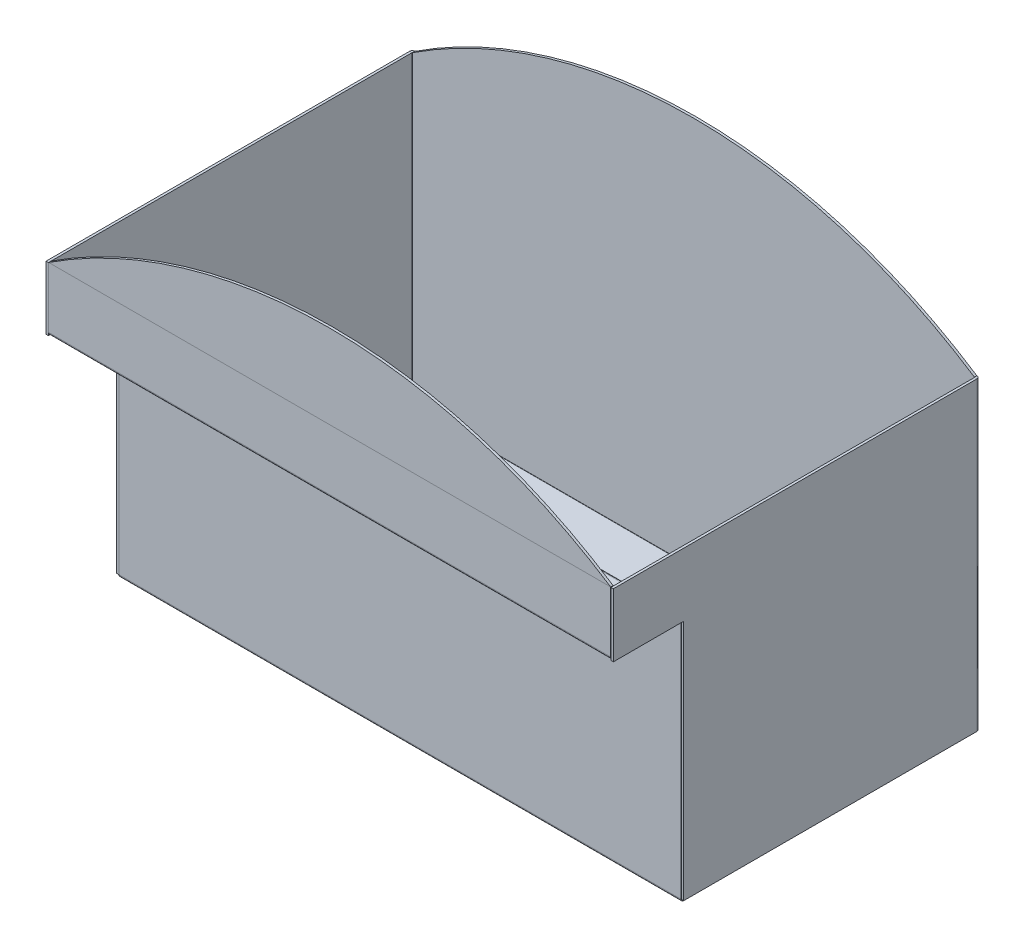
SolidWorks part; units mm, degrees
note: The reader was unsure of these and kept them because the rebuilt part matched: flange length of "Ребро-кромка1", "Ребро-кромка2", "Ребро-кромка3", "Ребро-кромка4", "Ребро-кромка5", "Ребро-кромка6".
ref_plane "Спереди" through (0, 0, 0) normal (0, 0, 1) x (1, 0, 0)
ref_plane "Сверху" through (0, 0, 0) normal (0, 1, 0) x (1, 0, 0)
ref_plane "Справа" through (0, 0, 0) normal (1, 0, 0) x (0, 0, -1)
sketch "Эскиз1" plane through (0, 0, 0) normal (0, 0, 1) x (1, 0, 0)
  line L3 (-97.6801, -33.9236) -> (134.0604, -33.9236)
  arc A0 (-97.6801, -33.9236) -> (134.0604, -33.9236) centre (18.1902, -211.1344) cw
extrude "Вытянуть1" add sketch "Эскиз1" along normal blind 1
sketch "Эскиз5" plane through (0, 0, 0) normal (0, 0, -1) x (-1, 0, 0)
  line L1 (-134.0604, -33.9236) -> (97.6801, -33.9236)
  line L2 (-134.0604, -33.9236) -> (-134.0604, -58.9236)
  line L3 (-134.0604, -58.9236) -> (97.6801, -58.9236)
  line L4 (97.6801, -33.9236) -> (97.6801, -58.9236)
sheet metal parameters "Листовой металл1" thickness 1 parameters "D1"=0.1
base flange "Базовая кромка1" sketch "Эскиз5" thickness 1 reverse thickness direction no parameters "D1"=0.1
edge flange "Ребро-кромка1" sketch "Эскиз9" flange angle 90 flange length 28 flange position bend outside bend radius 0.1 thickness 1 relief rectangular parameters "D6"=10
sketch "Эскиз9" plane through (0, -58.9236, 0) normal (0, -1, 0) x (-1, 0, 0)
  line L2 (-134.0604, 0) -> (-134.0604, 28)
  line L3 (-134.0604, 28) -> (97.6801, 28)
  line L4 (97.6801, 28) -> (97.6801, 0)
  line L6 (-134.0604, 0) -> (97.6801, 0) construction
  line L7 (-134.0604, 0) -> (97.6801, 0)
bend "EdgeBend1" bend radius 0.1 bend angle 90 parameters "D5"=1
edge flange "Ребро-кромка2" sketch "Эскиз12" flange angle 90 flange length 100 flange position material outside bend radius 0.1 thickness 1 relief rectangular parameters "D6"=10
sketch "Эскиз12" plane through (0, -60.0236, -28) normal (0, 0, 1) x (-1, 0, 0)
  line L1 (97.6801, 0) -> (-134.0604, 0) construction
  line L2 (-134.0604, 0) -> (-134.0604, 100)
  line L3 (-134.0604, 100) -> (97.6801, 100)
  line L4 (97.6801, 100) -> (97.6801, 0)
  line L5 (97.6801, 0) -> (-134.0604, 0)
bend "EdgeBend2" bend radius 0.1 bend angle 90 parameters "D5"=2
edge flange "Ребро-кромка3" sketch "Эскиз15" flange angle 90 flange length 120 flange position material outside bend radius 0.1 thickness 1 relief rectangular parameters "D6"=10
sketch "Эскиз15" plane through (0, -160.0236, -29) normal (0, 1, 0) x (1, 0, 0)
  line L2 (-97.6801, 0) -> (-97.6801, 120)
  line L3 (-97.6801, 120) -> (134.0604, 120)
  line L4 (134.0604, 120) -> (134.0604, 0)
  line L6 (134.0604, 0) -> (-97.6801, 0) construction
  line L7 (134.0604, 0) -> (-97.6801, 0)
bend "EdgeBend3" bend radius 0.1 bend angle 90 parameters "D5"=3
edge flange "Ребро-кромка4" sketch "Эскиз18" flange angle 90 flange length 126 flange position material outside bend radius 0.1 thickness 1 relief rectangular parameters "D6"=10
sketch "Эскиз18" plane through (0, -160.0236, -149) normal (0, 0, 1) x (1, 0, 0)
  line L1 (134.0604, 0) -> (-97.6801, 0) construction
  line L2 (-97.6801, 0) -> (-97.6801, 126)
  line L4 (134.0604, 126) -> (134.0604, 0)
  line L5 (134.0604, 0) -> (-97.6801, 0)
  arc A0 (134.0604, 126) -> (-97.6801, 126) centre (18.1902, -50.5991) ccw
bend "EdgeBend4" bend radius 0.1 bend angle 90 parameters "D5"=4
edge flange "Ребро-кромка5" sketch "Эскиз22" flange angle 90 flange length 150 flange position bend outside bend radius 0.1 thickness 1 relief rectangular parameters "D6"=10
sketch "Эскиз22" plane through (-97.6801, 0, -149) normal (1, 0, 0) x (0, 1, 0)
  line L1 (-34.0236, 0) -> (-159.9236, 0) construction
  line L2 (-159.9236, 0) -> (-159.9236, 150)
  line L3 (-159.9236, 150) -> (-34.0236, 150)
  line L4 (-34.0236, 150) -> (-34.0236, 0)
  line L5 (-34.0236, 0) -> (-159.9236, 0)
bend "EdgeBend5" bend radius 0.1 bend angle 90 parameters "D5"=5
edge flange "Ребро-кромка6" sketch "Эскиз25" flange angle 90 flange length 150 flange position bend outside bend radius 0.1 thickness 1 relief rectangular parameters "D6"=10
sketch "Эскиз25" plane through (134.0604, 0, -149) normal (-1, 0, 0) x (0, -1, 0)
  line L1 (159.9236, 0) -> (34.0236, 0) construction
  line L2 (34.0236, 0) -> (34.0236, 150)
  line L3 (34.0236, 150) -> (159.9236, 150)
  line L4 (159.9236, 150) -> (159.9236, 0)
  line L5 (159.9236, 0) -> (34.0236, 0)
bend "EdgeBend6" bend radius 0.1 bend angle 90 parameters "D5"=6
sketch "Эскиз33" plane through (-98.7801, 0, 0) normal (-1, 0, 0) x (0, 0, 1)
  line L0 (1, -159.9236) -> (-148.9, -159.9236) construction
  line L1 (-28, -60.1236) -> (1, -60.1236)
  line L2 (-28, -60.1236) -> (-28, -159.9236)
  line L3 (-28, -159.9236) -> (1, -159.9236)
  line L4 (1, -60.1236) -> (1, -159.9236)
  line L5 (1, -34.0236) -> (1, -159.9236) construction
extrude "Вытянуть4" cut sketch "Эскиз33" against normal through all normal cut yes
flat pattern "Развертка1" [suppressed]
sketch "Сгиб-Линии1" plane through (0, 0, 1) normal (0, 0, 1) x (1, 0, 0)
  line L0 (134.5317, -310.0935) -> (134.5317, -435.9935) construction
  line L1 (-98.1513, -435.9935) -> (-98.1513, -310.0935) construction
  line L2 (134.0604, -309.6223) -> (-97.6801, -309.6223) construction
  line L3 (134.0604, -188.8798) -> (-97.6801, -188.8798) construction
  line L4 (134.0604, -88.1373) -> (-97.6801, -88.1373) construction
  line L5 (134.5317, -310.0935) -> (134.5317, -435.9935) construction
  line L6 (-98.1513, -435.9935) -> (-98.1513, -310.0935) construction
  line L7 (134.0604, -59.3949) -> (-97.6801, -59.3949) construction
  line L8 (134.0604, -309.6223) -> (-97.6801, -309.6223) construction
  line L9 (134.0604, -188.8798) -> (-97.6801, -188.8798) construction
  line L10 (134.0604, -88.1373) -> (-97.6801, -88.1373) construction
  line L15 (134.0604, -59.3949) -> (-97.6801, -59.3949) construction
  point P0 (134.5317, -88.6661)
  point P1 (134.5317, -88.6661)
  point P2 (-98.1513, -88.6661)
  point P3 (-98.1513, -88.6661)
  point P4 (134.0604, -88.6661)
  point P5 (-97.6801, -88.6661)
  point P6 (134.0604, -88.6661)
  point P7 (-97.6801, -88.6661)
  point P12 (134.0604, -88.0373)
  point P13 (-97.6801, -88.0373)
bend of the flat pattern "Плоское состояние-<EdgeBend1>1"
bend of the flat pattern "Плоское состояние-<EdgeBend2>1"
bend of the flat pattern "Плоское состояние-<EdgeBend3>1"
bend of the flat pattern "Плоское состояние-<EdgeBend4>1"
bend of the flat pattern "Плоское состояние-<EdgeBend5>1"
bend of the flat pattern "Плоское состояние-<EdgeBend6>1"
